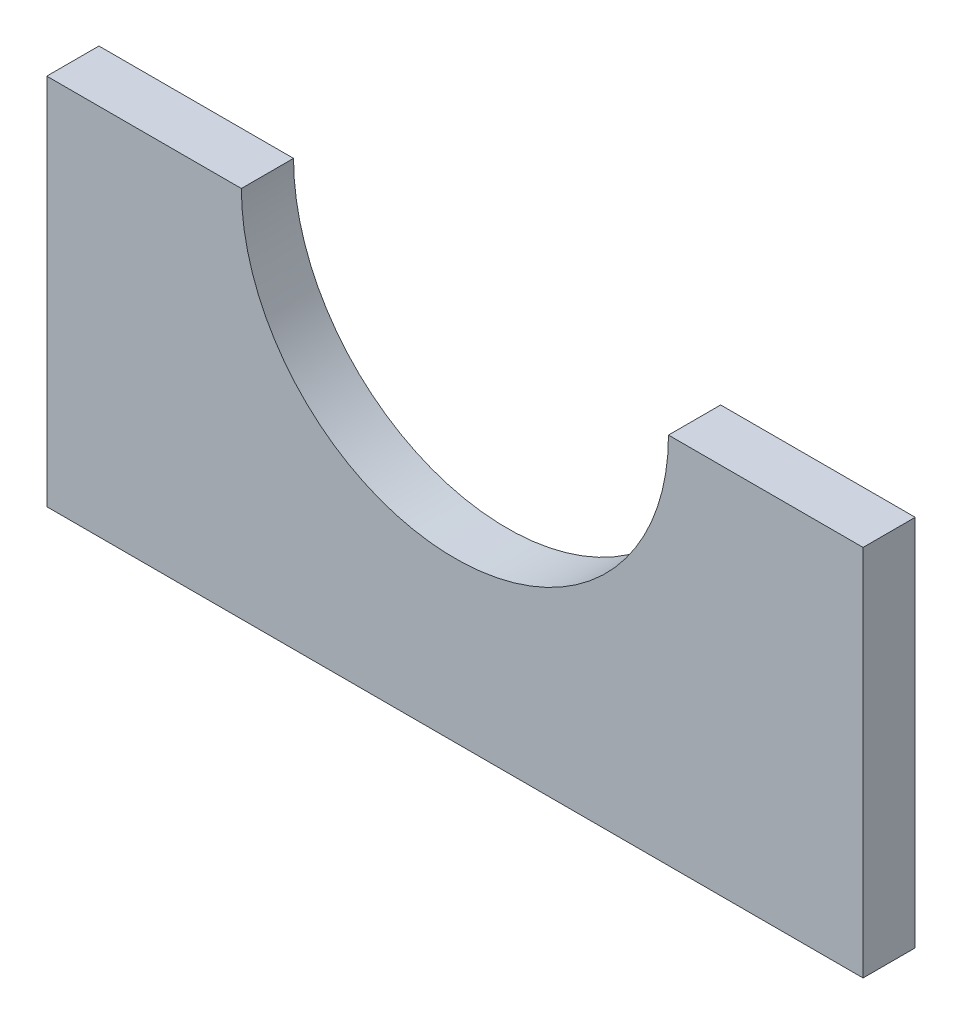
SolidWorks part; units mm, degrees
ref_plane "Front Plane" through (0, 0, 0) normal (0, 0, 1) x (1, 0, 0)
ref_plane "Top Plane" through (0, 0, 0) normal (0, 1, 0) x (1, 0, 0)
ref_plane "Right Plane" through (0, 0, 0) normal (1, 0, 0) x (0, 0, -1)
sketch "Sketch1" plane through (0, 0, 0) normal (0, 1, 0) x (1, 0, 0)
  line L1 (-19.845, 1.5875) -> (19.845, 1.5875)
  line L2 (-19.845, 1.5875) -> (-19.845, -1.5875)
  line L3 (-19.845, -1.5875) -> (19.845, -1.5875)
  line L4 (19.845, 1.5875) -> (19.845, -1.5875)
  line L5 (-19.845, 1.5875) -> (19.845, -1.5875) construction
  line L6 (-19.845, -1.5875) -> (19.845, 1.5875) construction
  point P0 (0, 0)
  dimension "D1" = 3.175
  dimension "D2" = 39.69
extrude "Boss-Extrude2" add sketch "Sketch1" along normal blind 12.7
ref_plane "Plane1" through (0, 0, 1.5875) normal (0, 0, 1) x (1, 0, 0)
sketch "Sketch3" plane through (0, 0, 1.5875) normal (0, 0, 1) x (1, 0, 0)
  line L0 (-19.845, 12.7) -> (19.845, 12.7) construction
  line L1 (-11, 12.7) -> (11, 12.7)
  arc A0 (11, 12.7) -> (-11, 12.7) centre (0, 12.7) cw
  dimension "D1" = 11
extrude "Cut-Extrude1" cut sketch "Sketch3" against normal blind 12.7
sketch "Sketch5" plane through (0, 0, 0) normal (0, 0, 1) x (1, 0, 0)
  line L0 (19.845, 12.7) -> (19.845, 0)
  line L1 (19.845, 0) -> (24.845, 0)
  line L2 (19.845, 12.7) -> (24.845, 12.7)
  line L3 (24.845, 12.7) -> (24.845, 0)
  line L5 (-19.845, 12.7) -> (-19.845, 0)
  line L6 (-19.845, 0) -> (-24.845, 0)
  line L7 (-24.845, 12.7) -> (-24.845, 0)
  line L8 (-19.845, 12.7) -> (-24.845, 12.7)
  dimension "D1" = 5
extrude "Boss-Extrude3" add sketch "Sketch5" along normal blind 1.5875 and the other way blind 1.5875
sketch "Sketch6" plane through (0, 0, 1.5875) normal (0, 0, 1) x (1, 0, 0)
  line L0 (-24.845, 0) -> (24.845, 0)
  line L1 (24.845, 0) -> (24.845, -5)
  line L2 (-24.845, 0) -> (-24.845, -5)
  line L3 (-24.845, -5) -> (24.845, -5)
  dimension "D1" = 5
extrude "Boss-Extrude4" add sketch "Sketch6" against normal blind 3.175
sketch "Sketch7" plane through (0, 0, 1.5875) normal (0, 0, 1) x (1, 0, 0)
  line L0 (-11, 12.7) -> (11, 12.7)
  line L1 (-24.845, 12.7) -> (-11, 12.7) construction
  line L2 (11, 12.7) -> (24.845, 12.7) construction
  line L3 (-13, 12.7) -> (-11, 12.7)
  line L4 (13, 12.7) -> (11, 12.7)
  arc A0 (-11, 12.7) -> (11, 12.7) centre (0, 12.7) ccw construction
  arc A1 (-11, 12.7) -> (11, 12.7) centre (0, 12.7) ccw
  arc A2 (-13, 12.7) -> (13, 12.7) centre (0, 12.7) ccw
  line M1 (24.845, 12.7) -> (11, 12.7)
  arc M2 (11, 12.7) -> (-11, 12.7) centre (0, 12.7) cw
  line M3 (-11, 12.7) -> (-24.845, 12.7)
  dimension "D1" = 13
extrude "Cut-Extrude2" cut sketch "Sketch7" against normal blind 3.175 contours A2 M3 M1 M2 region at (0, 1.4093, 1.5875)
sketch "Sketch8" plane through (0, 0, 1.5875) normal (0, 0, 1) x (1, 0, 0)
  line L0 (-24.845, -5) -> (24.845, -5)
  line L1 (24.845, -5) -> (24.845, -10)
  line L2 (-24.845, -5) -> (-24.845, -10)
  line L3 (-24.845, -10) -> (24.845, -10)
  dimension "D1" = 5
extrude "Boss-Extrude5" add sketch "Sketch8" against normal blind 3.175
